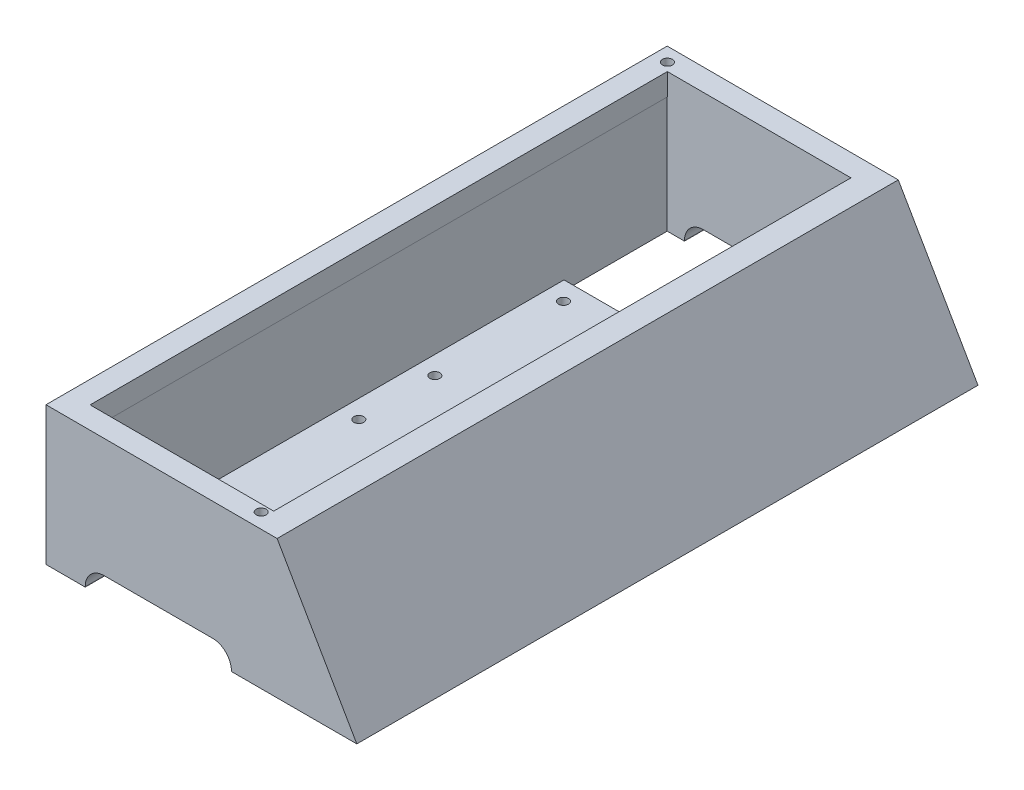
SolidWorks part; units mm, degrees
ref_plane "Alzado" through (0, 0, 0) normal (0, 0, 1) x (1, 0, 0)
ref_plane "Planta" through (0, 0, 0) normal (0, 1, 0) x (1, 0, 0)
ref_plane "Vista lateral" through (0, 0, 0) normal (1, 0, 0) x (0, 0, -1)
sketch "Sketch1" plane through (0, 0, 0) normal (0, 0, 1) x (1, 0, 0)
  line L0 (0, 0) -> (99.07, 0)
  line L1 (99.07, 0) -> (73.665, 44.0028)
  line L2 (0, 0) -> (0, 44.1)
  line L3 (0, 44.1) -> (73.665, 44.0028)
  dimension "D1" = 99.07
  dimension "D2" = 60
  dimension "D3" = 50.81
  dimension "D4" = 44.1
  dimension "D5" = 90
extrude "Boss-Extrude1" add sketch "Sketch1" along normal blind 198
shell "Shell1" thickness 7 removed face at (49.535, 0, 99)
sketch "Sketch2" plane through (68.2403, 39.3986, 0) normal (-0.866, -0.5, 0) x (0, 0, 1)
  line L0 (191, -3.5) -> (191, -45.4935) construction
  line L1 (7, -45.4935) -> (191, -45.4935)
  line L2 (7, -45.4935) -> (7, 46.3403)
  line L3 (7, 46.3403) -> (191, 46.3403)
  line L4 (191, -45.4935) -> (191, 46.3403)
  line L5 (7, -45.4935) -> (7, -2.7603) construction
  dimension "D1" = 0
  dimension "D2" = 0
extrude "Cut-Extrude1" cut sketch "Sketch2" along normal blind 10
sketch "Sketch3" plane through (0.0582, 44.0999, 0) normal (0.0013, 1, 0) x (1, -0.0013, 0)
  line L0 (7, -7) -> (90.987, -7) construction
  line L1 (7, -191) -> (58.0157, -191)
  line L2 (7, -191) -> (7, -7)
  line L3 (7, -7) -> (58.0157, -7)
  line L4 (58.0157, -191) -> (58.0157, -7)
  line L5 (7, -191) -> (90.987, -191) construction
  line L6 (7, -191) -> (7, -7) construction
  line L7 (58.0157, -7) -> (58.0157, -191) construction
  dimension "D1" = 0
  dimension "D2" = 0
  dimension "D3" = 0
  dimension "D4" = 0
extrude "Cut-Extrude3" cut sketch "Sketch3" against normal blind 10
sketch "Sketch4" plane through (0, 0, 0) normal (0, -1, 0) x (1, 0, 0)
  line L0 (7, 191) -> (7, 158.11) construction
  line L1 (7.049, 7) -> (7.049, 39.89) construction
  line L2 (90.9871, 191) -> (90.9871, 7) construction
  line L3 (7, 158.11) -> (50.2271, 158.11)
  line L4 (7, 158.11) -> (7, 39.89)
  line L5 (7, 39.89) -> (50.2271, 39.89)
  line L6 (50.2271, 158.11) -> (50.2271, 39.89)
  line L7 (7, 191) -> (90.9871, 191) construction
  line L8 (7, 7) -> (90.9871, 7) construction
  line L15 (90.9871, 81) -> (80.9871, 81)
  line L16 (90.9871, 81) -> (90.9871, 91)
  line L17 (90.9871, 91) -> (80.9871, 91)
  line L18 (80.9871, 81) -> (80.9871, 91)
  dimension "D1" = 32.89
  dimension "D2" = 32.89
  dimension "D3" = 40.76
  dimension "D4" = 32.89
  dimension "D5" = 32.89
  dimension "D8" = 10
  dimension "D10" = 0
extrude "Boss-Extrude2" add sketch "Sketch4" against normal blind 3
sketch "Sketch6" plane through (0, 3, 0) normal (0, 1, 0) x (1, 0, 0)
  circle A0 centre (12.8305, -45.8872) radius 1.585
  circle A1 centre (12.8305, -86.8872) radius 1.585
  circle A2 centre (12.8305, -111.1128) radius 1.585
  circle A3 centre (12.8305, -152.1128) radius 1.585
extrude "Cut-Extrude5" cut sketch "Sketch6" against normal blind 10
sketch "Sketch10" plane through (0, 0, 0) normal (0, -1, 0) x (1, 0, 0)
  circle A0 centre (84.0927, 85.7391) radius 1.585
extrude "Cut-Extrude8" cut sketch "Sketch10" against normal blind 5
sketch "Sketch9" plane through (0, 0, 198) normal (0, 0, 1) x (1, 0, 0)
  line L0 (0, 44.1) -> (0, 0) construction
  line L1 (12.5, 0) -> (59.0927, 0)
  line L2 (12.5, 0) -> (12.5, 6.1795)
  line L3 (12.5, 6.1795) -> (59.0927, 6.1795)
  line L4 (59.0927, 0) -> (59.0927, 6.1795)
  line L5 (71.5927, -45.1936) -> (71.5927, 0) construction
  dimension "D1" = 12.5
  dimension "D2" = 12.5
extrude "Cut-Extrude7" cut sketch "Sketch9" against normal blind 10
ref_plane "Plane1" through (0, 0, 99) normal (0, 0, -1) x (-1, 0, 0)
mirror "Mirror1" about plane through (0, 0, 99) normal (0, 0, -1) of "Cut-Extrude7"
fillet "Fillet1" radius 6 2 edges at (12.5, 6.1795, 3.5) (59.0927, 6.1795, 3.5)
fillet "Fillet2" radius 6 2 edges at (59.0927, 6.1795, 194.5) (12.5, 6.1795, 194.5)
mirror "Mirror2" about plane through (0, 0, 99) normal (0, 0, -1) of "Boss-Extrude2", "Cut-Extrude8"
sketch "Sketch11" plane through (0, 0, 0) normal (0, -1, 0) x (1, 0, 0)
  circle A0 centre (12.8305, 152.1128) radius 1.585
  circle A1 centre (12.8305, 111.1128) radius 1.585
  circle A2 centre (12.8305, 86.8872) radius 1.585
  circle A3 centre (12.8305, 45.8872) radius 1.585
extrude "Cut-Extrude9" cut sketch "Sketch11" against normal blind 5
sketch "Sketch12" plane through (0.0582, 44.0999, 0) normal (0.0013, 1, 0) x (1, -0.0013, 0)
  circle A0 centre (63.7683, -193.2457) radius 1.585
  circle A1 centre (4.417, -4.4022) radius 1.585
  dimension "D1" = 3.17
  dimension "D2" = 3.17
extrude "Cut-Extrude10" cut sketch "Sketch12" against normal blind 5
